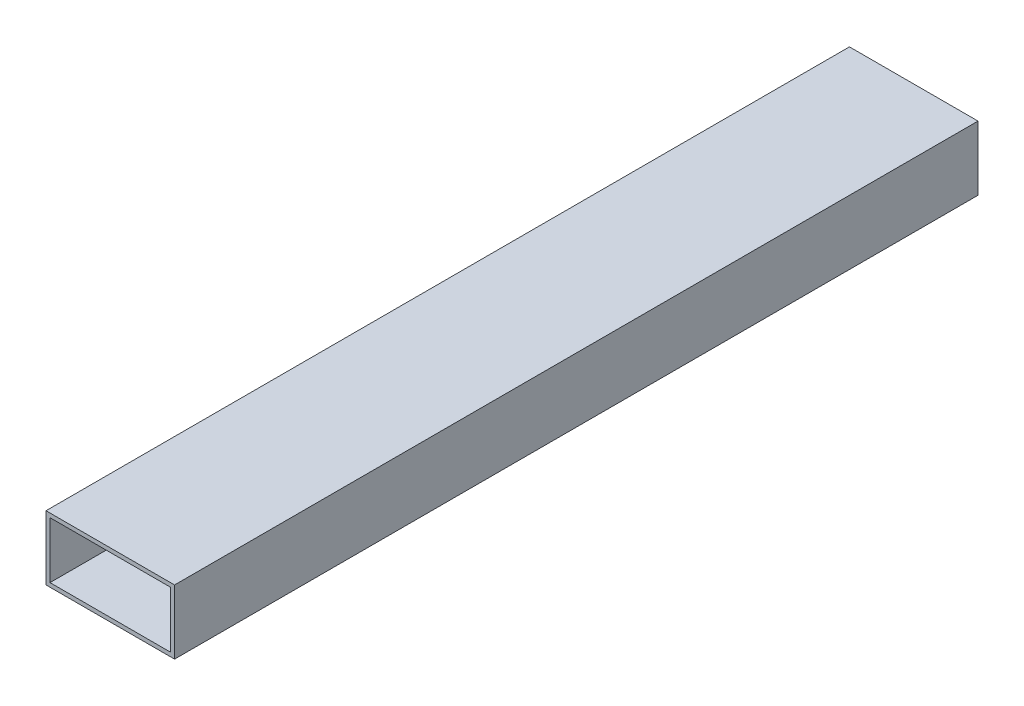
SolidWorks part; units mm, degrees
ref_plane "Front Plane" through (0, 0, 0) normal (0, 0, 1) x (1, 0, 0)
ref_plane "Top Plane" through (0, 0, 0) normal (0, 1, 0) x (1, 0, 0)
ref_plane "Right Plane" through (0, 0, 0) normal (1, 0, 0) x (0, 0, -1)
sketch "Sketch1" plane through (0, 0, 0) normal (0, 0, 1) x (1, 0, 0)
  line L0 (-23.8125, 11.1125) -> (23.8125, 11.1125)
  line L2 (-25.4, 12.7) -> (25.4, 12.7)
  line L3 (-25.4, 12.7) -> (-25.4, -12.7)
  line L4 (-25.4, -12.7) -> (25.4, -12.7)
  line L5 (25.4, 12.7) -> (25.4, -12.7)
  line L10 (23.8125, 11.1125) -> (23.8125, -11.1125)
  line L11 (-23.8125, -11.1125) -> (23.8125, -11.1125)
  line L12 (-23.8125, 11.1125) -> (-23.8125, -11.1125)
  point P12 (0, 12.7)
  point P14 (25.4, 0)
  dimension "Wall Thickness" = 1.5875
  dimension "Outside Width" = 50.8
  dimension "Outside Height" = 25.4
  dimension "Inside Height" = 22.225
  dimension "Inside Width" = 47.625
sketch "Sketch2" plane through (0, 0, 0) normal (1, 0, 0) x (0, 0, -1)
  line L0 (158.75, 0) -> (-158.75, 0)
  point P4 (0, 0)
  point P7 (-158.75, 0)
  point P10 (158.75, 0)
  dimension "Length" = 317.5
sketch "Sketch3" plane through (0, 0, 0) normal (0, 0, 1) x (1, 0, 0)
  line L21 (25.4, 12.7) -> (-25.4, 12.7)
  line L22 (25.4, -12.7) -> (25.4, 12.7)
  line L23 (-25.4, -12.7) -> (25.4, -12.7)
  line L24 (-25.4, 12.7) -> (-25.4, -12.7)
  line L25 (25.4, 12.7) -> (-25.4, 12.7)
  line L26 (25.4, -12.7) -> (25.4, 12.7)
  line L27 (-25.4, -12.7) -> (25.4, -12.7)
  line L28 (-25.4, 12.7) -> (-25.4, -12.7)
  line L29 (23.8125, 11.1125) -> (-23.8125, 11.1125)
  line L30 (23.8125, -11.1125) -> (23.8125, 11.1125)
  line L31 (-23.8125, -11.1125) -> (23.8125, -11.1125)
  line L32 (-23.8125, 11.1125) -> (-23.8125, -11.1125)
  line L33 (23.8125, 11.1125) -> (-23.8125, 11.1125)
  line L34 (23.8125, -11.1125) -> (23.8125, 11.1125)
  line L35 (-23.8125, -11.1125) -> (23.8125, -11.1125)
  line L36 (-23.8125, 11.1125) -> (-23.8125, -11.1125)
  dimension "D1" = 0
  dimension "D2" = 0
extrude "Boss-Extrude1" add sketch "Sketch3" along normal up to vertex (158.75 mm away) and the other way up to vertex (158.75 mm away) up to point (0, 0, 158.75) other way up to point (0, 0, -158.75)
sketch "Drawing Reference" plane through (0, 0, 0) normal (1, 0, 0) x (0, 0, -1)
  line L0 (-158.75, 0) -> (158.75, 0) construction
  line L1 (0, -12.7) -> (0, 12.7) construction
  line L2 (-158.75, -12.7) -> (158.75, -12.7) construction
  line L5 (-158.75, 12.7) -> (158.75, 12.7) construction
  point P7 (-122.174, 0)
  point P8 (122.174, 0)
  dimension "D1" = 36.576
equation "\"D1@Drawing Reference\"=\"Outside Width@Sketch1\" * 0.72"
